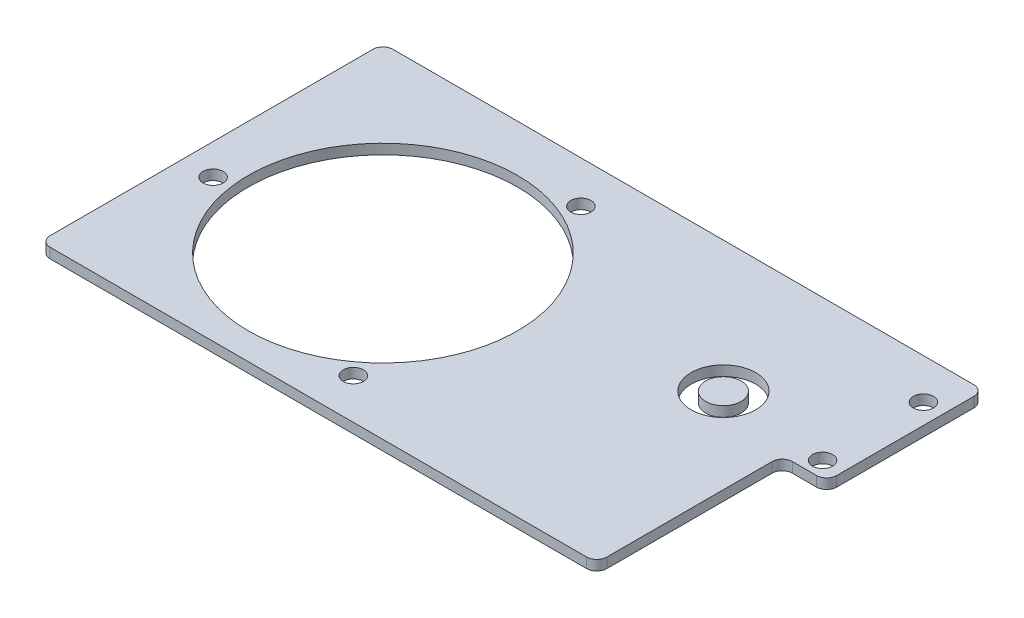
SolidWorks part; units mm, degrees
ref_plane "Front Plane" through (0, 0, 0) normal (0, 0, 1) x (1, 0, 0)
ref_plane "Top Plane" through (0, 0, 0) normal (0, 1, 0) x (1, 0, 0)
ref_plane "Right Plane" through (0, 0, 0) normal (1, 0, 0) x (0, 0, -1)
sketch "Sketch1" plane through (0, 0, 0) normal (0, 1, 0) x (1, 0, 0)
  line L0 (0, 114.3) -> (0, -101.6) construction
  line L1 (257.81, 114.3) -> (-107.95, 114.3)
  line L2 (264.16, 107.95) -> (264.16, 21.59)
  line L3 (229.87, -101.6) -> (-107.95, -101.6)
  line L4 (-114.3, 107.95) -> (-114.3, -95.25)
  line L5 (242.57, 15.24) -> (257.81, 15.24)
  line L6 (251.46, 0) -> (251.46, 114.3) construction
  line L7 (-114.3, 0) -> (285.75, 0) construction
  line L8 (0, 0) -> (-114.3, -39.3566) construction
  line L11 (236.22, -95.25) -> (236.22, 8.89)
  circle A0 centre (0, 0) radius 84.7725
  circle A1 centre (0, 0) radius 95.25 construction
  circle A2 centre (-94.8682, -12.0662) radius 6.35
  arc A3 (236.22, 8.89) -> (242.57, 15.24) centre (242.57, 8.89) cw
  arc A4 (-107.95, 114.3) -> (-114.3, 107.95) centre (-107.95, 107.95) ccw
  circle A5 centre (36.7916, 87.8575) radius 6.35
  circle A6 centre (57.4982, -76.1251) radius 6.35
  arc A7 (-107.95, -101.6) -> (-114.3, -95.25) centre (-107.95, -95.25) cw
  arc A8 (229.87, -101.6) -> (236.22, -95.25) centre (229.87, -95.25) ccw
  arc A9 (257.81, 15.24) -> (264.16, 21.59) centre (257.81, 21.59) ccw
  arc A10 (257.81, 114.3) -> (264.16, 107.95) centre (257.81, 107.95) cw
  circle A11 centre (251.46, 88.9) radius 6.35
  circle A12 centre (251.46, 25.4) radius 6.35
  circle A13 centre (-94.8682, -12.0662) radius 6.35 construction
  point P0 (0, 0)
  point P11 (0, 0)
  point P21 (236.22, -6.35)
  point P32 (236.22, -101.6)
  point P46 (-0.1928, -0.1113)
  dimension "D3" = 169.545
  dimension "D5" = 190.5
  dimension "D6" = 12.7
  dimension "D7" = 114.3
  dimension "D8" = 264.16
  dimension "D11" = 6.35
  dimension "D12" = 86.36
  dimension "D14" = 12.7
  dimension "D1" = 114.3
  dimension "D2" = 101.6
  dimension "D4" = 19
  dimension "D9" = 95.25
  dimension "D10" = 27.94
  dimension "D13" = 12.7
  dimension "D15" = 25.4
  dimension "D16" = 3
extrude "Boss-Extrude1" add sketch "Sketch1" along normal blind 6.35
sketch "Sketch2" plane through (0, 0, 0) normal (0, -1, 0) x (1, 0, 0)
  line L0 (-114.3, -107.95) -> (-114.3, 95.25) construction
  line L1 (257.81, -114.3) -> (-107.95, -114.3) construction
  line L2 (264.16, -21.59) -> (264.16, -107.95) construction
  line L3 (-107.95, 101.6) -> (229.87, 101.6) construction
  line L4 (-114.3, -107.95) -> (-114.3, 95.25)
  line L5 (257.81, -114.3) -> (-107.95, -114.3)
  line L6 (264.16, -21.59) -> (264.16, -107.95)
  line L7 (-107.95, 101.6) -> (229.87, 101.6)
  line L8 (74.93, -114.3) -> (74.93, 101.6) construction
  line L9 (-114.3, -6.35) -> (264.16, -6.35) construction
  line L11 (319.405, 146.05) -> (-169.545, 146.05)
  line L12 (319.405, 146.05) -> (319.405, -158.75)
  line L13 (319.405, -158.75) -> (-169.545, -158.75)
  line L14 (-169.545, 146.05) -> (-169.545, -158.75)
  line L15 (319.405, 146.05) -> (-169.545, -158.75) construction
  line L16 (319.405, -158.75) -> (-169.545, 146.05) construction
  point P12 (74.93, -6.35)
  dimension "D1" = 378.46
  dimension "D2" = 215.9
  dimension "D3" = 488.95
  dimension "D4" = 304.8
sketch "Sketch3" plane through (0, 6.35, 0) normal (0, 1, 0) x (1, 0, 0)
  circle A0 centre (0, 0) radius 84.7725 construction
  point P0 (84.7725, 0)
sketch "Sketch4" plane through (0, 6.35, 0) normal (0, 1, 0) x (1, 0, 0)
  circle A1 centre (182.5001, 31.9035) radius 37.2826 construction
  circle A2 centre (182.5001, 31.9035) radius 20.32
  circle A3 centre (182.5001, 31.9035) radius 11.176 construction
  circle A4 centre (182.5001, 31.9035) radius 11.176
  dimension "D1" = 40.64
extrude "Cut-Extrude1" cut sketch "Sketch4" against normal blind 9.652
